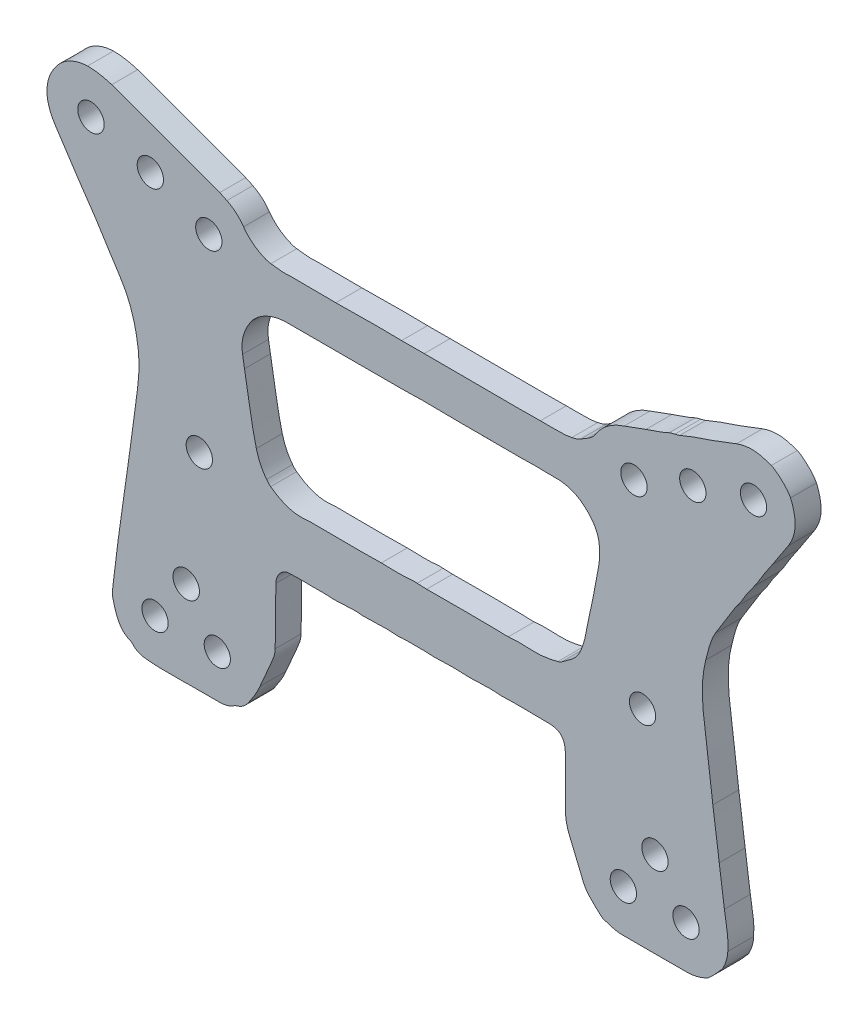
SolidWorks part; units mm, degrees
ref_plane "Front Plane" through (0, 0, 0) normal (0, 0, 1) x (1, 0, 0)
ref_plane "Top Plane" through (0, 0, 0) normal (0, 1, 0) x (1, 0, 0)
ref_plane "Right Plane" through (0, 0, 0) normal (1, 0, 0) x (0, 0, -1)
sketch "Model" plane through (0, 0, 0) normal (0, 0, 1) x (1, 0, 0)
  line L0 (97.8366, 172.2315) -> (110.3202, 167.6614)
  line L1 (138.5537, 158.5268) -> (149.5237, 158.5046)
  line L2 (118.384, 158.5261) -> (142.6959, 158.5291)
  circle A0 centre (95.4309, 167.7888) radius 1.5304
  circle A1 centre (102.2995, 165.6819) radius 1.5241
  circle A2 centre (109.0626, 162.8443) radius 1.5213
  circle A3 centre (158.2387, 162.8424) radius 1.5235
  circle A4 centre (165.0434, 165.6588) radius 1.5236
  circle A5 centre (172.0646, 167.7518) radius 1.5232
  circle A6 centre (159.2267, 140.4078) radius 1.5181
  circle A7 centre (107.9617, 140.4627) radius 1.5202
  circle A8 centre (102.8428, 121.5314) radius 1.5152
  circle A9 centre (110.0426, 121.522) radius 1.515
  circle A10 centre (106.448, 126.5199) radius 1.531
  circle A11 centre (160.6629, 126.5138) radius 1.5206
  circle A12 centre (157.0119, 121.5008) radius 1.522
  circle A13 centre (164.2554, 121.513) radius 1.5157
  spline S0 degree 2 poles (95.0441, 172.7052) (96.4811, 172.6765) (97.8366, 172.2315) knots 0 0 0 1 1 1
  spline S1 degree 2 poles (110.3202, 167.6614) (112.1413, 166.9415) (113.1909, 165.4568) knots 0 0 0 1 1 1
  spline S85 degree 3 poles (103.4626, 116.5865) (104.4481, 116.5653) (105.4344, 116.5808) (106.4204, 116.5808) knots 115 115 115 115 116 116 116 116
  spline S86 degree 3 poles (101.611, 116.719) (102.2249, 116.6461) (102.8445, 116.5998) (103.4626, 116.5865) knots 114 114 114 114 115 115 115 115
  spline S87 degree 3 poles (100.2756, 117.3777) (100.6348, 116.9744) (101.0987, 116.7799) (101.611, 116.719) knots 113 113 113 113 114 114 114 114
  spline S88 degree 3 poles (99.8652, 117.6628) (100.0163, 117.5998) (100.1675, 117.4992) (100.2756, 117.3777) knots 112 112 112 112 113 113 113 113
  spline S89 degree 3 poles (98.4441, 119.2638) (98.7327, 118.5809) (99.1304, 117.9689) (99.8652, 117.6628) knots 111 111 111 111 112 112 112 112
  spline S90 degree 3 poles (97.9974, 120.7159) (98.1355, 120.2283) (98.2479, 119.7279) (98.4441, 119.2638) knots 110 110 110 110 111 111 111 111
  spline S91 degree 3 poles (98.5644, 126.9173) (98.3475, 125.2708) (98.1634, 123.62) (97.9521, 121.9727) (97.8976, 121.5475) (97.8803, 121.1292) (97.9974, 120.7159) knots 108 108 108 108 109 109 109 110 110 110 110
  spline S92 degree 3 poles (99.279, 132.023) (99.0385, 130.3214) (98.7888, 128.621) (98.5644, 126.9173) knots 107 107 107 107 108 108 108 108
  spline S93 degree 3 poles (99.71, 135.0345) (99.5692, 134.0303) (99.421, 133.0271) (99.279, 132.023) knots 106 106 106 106 107 107 107 107
  spline S94 degree 3 poles (100.9053, 147.204) (101.0652, 145.9154) (100.9832, 144.613) (100.8239, 143.3237) (100.6236, 141.7024) (100.3996, 140.0841) (100.1819, 138.4651) (100.0282, 137.3211) (99.8702, 136.1776) (99.71, 135.0345) knots 103 103 103 103 104 104 104 105 105 105 106 106 106 106
  spline S95 degree 3 poles (98.7922, 153.4778) (100.0504, 151.5722) (100.6288, 149.4314) (100.9053, 147.204) knots 102 102 102 102 103 103 103 103
  spline S96 degree 3 poles (97.5576, 155.3954) (97.9657, 154.7539) (98.3733, 154.1122) (98.7922, 153.4778) knots 101 101 101 101 102 102 102 102
  spline S97 degree 3 poles (96.0248, 157.8234) (96.0565, 157.7768) (96.0853, 157.7282) (96.1154, 157.6806) (96.5959, 156.9187) (97.0742, 156.1554) (97.5576, 155.3954) knots 99 99 99 99 100 100 100 101 101 101 101
  spline S98 degree 3 poles (93.84, 161.0383) (94.5617, 159.9622) (95.2962, 158.8948) (96.0248, 157.8234) knots 98 98 98 98 99 99 99 99
  spline S99 degree 3 poles (91.5674, 164.5) (91.7649, 164.192) (91.9685, 163.8879) (92.1693, 163.5819) (92.7257, 162.7337) (93.275, 161.8807) (93.84, 161.0383) knots 96 96 96 96 97 97 97 98 98 98 98
  spline S100 degree 3 poles (90.9869, 165.4325) (91.1606, 165.111) (91.3697, 164.8083) (91.5674, 164.5) knots 95 95 95 95 96 96 96 96
  spline S101 degree 3 poles (95.0441, 172.7052) (93.229, 172.6106) (91.841, 171.7447) (90.9786, 170.2059) (90.114, 168.663) (90.1293, 167.02) (90.9869, 165.4325) knots 93 93 93 93 94 94 94 95 95 95 95
  spline S102 degree 3 poles (96.0103, 172.4602) (95.6857, 172.5087) (95.4054, 172.7241) (95.0441, 172.7052) knots 92 92 92 92 93 93 93 93 construction
  spline S103 degree 3 poles (96.927, 172.4812) (96.6208, 172.4791) (96.3079, 172.4157) (96.0103, 172.4602) knots 91 91 91 91 92 92 92 92 construction
  spline S104 degree 3 poles (98.9897, 171.7424) (98.3769, 171.9508) (97.7507, 172.1161) (97.1662, 172.4023) (97.091, 172.4392) (97.0067, 172.4818) (96.927, 172.4812) knots 89 89 89 89 90 90 90 91 91 91 91
  spline S105 degree 3 poles (101.6624, 170.6911) (100.773, 171.0459) (99.8951, 171.4344) (98.9897, 171.7424) knots 88 88 88 88 89 89 89 89
  spline S106 degree 3 poles (101.8161, 170.6222) (101.7627, 170.6298) (101.7147, 170.6702) (101.6624, 170.6911) knots 87 87 87 87 88 88 88 88
  spline S107 degree 3 poles (104.6139, 169.6781) (103.6743, 169.9742) (102.8069, 170.4816) (101.8161, 170.6222) knots 86 86 86 86 87 87 87 87
  spline S108 degree 3 poles (107.4638, 168.6149) (106.5143, 168.9714) (105.5796, 169.3738) (104.6139, 169.6781) knots 85 85 85 85 86 86 86 86
  spline S109 degree 3 poles (108.3376, 168.305) (108.0458, 168.4068) (107.7531, 168.5063) (107.4638, 168.6149) knots 84 84 84 84 85 85 85 85
  spline S110 degree 3 poles (109.5336, 167.8891) (109.1368, 168.033) (108.7361, 168.1659) (108.3376, 168.305) knots 83 83 83 83 84 84 84 84
  spline S111 degree 3 poles (110.3202, 167.5828) (110.0506, 167.6588) (109.7981, 167.7932) (109.5336, 167.8891) knots 82 82 82 82 83 83 83 83
  spline S112 degree 3 poles (113.0796, 165.6093) (112.3882, 166.5926) (111.4799, 167.2557) (110.3202, 167.5828) knots 81 81 81 81 82 82 82 82
  spline S113 degree 3 poles (116.2355, 163.4985) (116.0147, 163.5296) (115.7899, 163.5808) (115.5847, 163.6657) (114.5736, 164.084) (113.7131, 164.7082) (113.0796, 165.6093) knots 79 79 79 79 80 80 80 81 81 81 81
  spline S114 degree 3 poles (123.7475, 163.3393) (122.1428, 163.3359) (120.5381, 163.3604) (118.9334, 163.3717) (118.7643, 163.3729) (118.5941, 163.3786) (118.426, 163.3642) (117.6889, 163.3012) (116.9615, 163.3966) (116.2355, 163.4985) knots 76 76 76 76 77 77 77 78 78 78 79 79 79 79
  spline S115 degree 3 poles (131.3554, 163.3539) (130.4536, 163.3588) (129.5517, 163.3926) (128.65, 163.3884) (127.0158, 163.3809) (125.3817, 163.3426) (123.7475, 163.3393) knots 74 74 74 74 75 75 75 76 76 76 76
  spline S116 degree 3 poles (133.9742, 163.362) (133.1013, 163.3641) (132.2283, 163.3491) (131.3554, 163.3539) knots 73 73 73 73 74 74 74 74
  spline S117 degree 3 poles (147.4146, 163.3507) (145.5577, 163.2892) (143.6967, 163.3532) (141.8374, 163.3579) (141.0485, 163.3599) (140.2594, 163.34) (139.4704, 163.3415) (137.6383, 163.3449) (135.8063, 163.3577) (133.9742, 163.362) knots 70 70 70 70 71 71 71 72 72 72 73 73 73 73
  spline S118 degree 3 poles (151.0431, 163.4841) (149.8395, 163.2374) (148.6229, 163.3906) (147.4146, 163.3507) knots 69 69 69 69 70 70 70 70
  spline S119 degree 3 poles (152.0682, 163.85) (151.7528, 163.6502) (151.4083, 163.5589) (151.0431, 163.4841) knots 68 68 68 68 69 69 69 69
  spline S120 degree 3 poles (152.8653, 164.3297) (152.5965, 164.1751) (152.3301, 164.016) (152.0682, 163.85) knots 67 67 67 67 68 68 68 68
  spline S121 degree 3 poles (153.8953, 165.3107) (153.6303, 164.8973) (153.2891, 164.5735) (152.8653, 164.3297) knots 66 66 66 66 67 67 67 67
  spline S122 degree 3 poles (157.0904, 167.6614) (155.7611, 167.2261) (154.6586, 166.5011) (153.8953, 165.3107) knots 65 65 65 65 66 66 66 66
  spline S123 degree 3 poles (159.6279, 168.594) (158.7861, 168.2724) (157.9463, 167.9416) (157.0904, 167.6614) knots 64 64 64 64 65 65 65 65
  spline S124 degree 3 poles (162.3171, 169.5994) (161.4534, 169.1745) (160.5217, 168.9354) (159.6279, 168.594) knots 63 63 63 63 64 64 64 64
  spline S125 degree 3 poles (162.9657, 169.7875) (162.7485, 169.727) (162.516, 169.6972) (162.3171, 169.5994) knots 62 62 62 62 63 63 63 63
  spline S126 degree 3 poles (163.5345, 169.9491) (163.3555, 169.871) (163.1557, 169.8406) (162.9657, 169.7875) knots 61 61 61 61 62 62 62 62
  spline S127 degree 3 poles (170.0977, 172.3863) (169.1745, 172.049) (168.2721, 171.6518) (167.3408, 171.3399) (166.0587, 170.9106) (164.7751, 170.4909) (163.5345, 169.9491) knots 59 59 59 59 60 60 60 61 61 61 61
  spline S128 degree 3 poles (174.1315, 172.2315) (173.8233, 172.364) (173.4887, 172.4355) (173.1653, 172.5323) (172.1259, 172.8434) (171.1013, 172.7529) (170.0977, 172.3863) knots 57 57 57 57 58 58 58 59 59 59 59
  spline S129 degree 3 poles (176.3428, 170.088) (176.0534, 170.7614) (174.8057, 171.9416) (174.1315, 172.2315) knots 56 56 56 56 57 57 57 57
  spline S130 degree 3 poles (176.0878, 165.1701) (177.1359, 166.7607) (177.062, 168.4146) (176.3428, 170.088) knots 55 55 55 55 56 56 56 56
  spline S131 degree 3 poles (174.2803, 162.413) (174.9051, 163.3166) (175.4831, 164.2524) (176.0878, 165.1701) knots 54 54 54 54 55 55 55 55
  spline S132 degree 3 poles (172.2116, 159.2264) (172.315, 159.3598) (172.4182, 159.4961) (172.5007, 159.6428) (173.04, 160.601) (173.6553, 161.509) (174.2803, 162.413) knots 52 52 52 52 53 53 53 54 54 54 54
  spline S133 degree 3 poles (169.9768, 155.9499) (170.2168, 156.3303) (170.5443, 156.6596) (170.7558, 157.0531) (171.1719, 157.827) (171.6763, 158.5353) (172.2116, 159.2264) knots 50 50 50 50 51 51 51 52 52 52 52
  spline S134 degree 3 poles (167.6641, 152.2135) (168.4105, 153.4736) (169.1952, 154.7112) (169.9768, 155.9499) knots 49 49 49 49 50 50 50 50
  spline S135 degree 3 poles (166.5414, 148.9484) (166.829, 150.0678) (167.0683, 151.2077) (167.6641, 152.2135) knots 48 48 48 48 49 49 49 49
  spline S136 degree 3 poles (167.3622, 134.8553) (167.039, 137.3418) (166.7576, 139.8341) (166.4095, 142.317) (166.098, 144.5395) (165.9756, 146.7465) (166.5414, 148.9484) knots 46 46 46 46 47 47 47 48 48 48 48
  spline S137 degree 3 poles (168.1024, 129.4132) (167.8552, 131.2272) (167.5982, 133.0399) (167.3622, 134.8553) knots 45 45 45 45 46 46 46 46
  spline S138 degree 3 poles (168.6967, 125.0588) (168.4941, 126.5096) (168.3003, 127.9617) (168.1024, 129.4132) knots 44 44 44 44 45 45 45 45
  spline S139 degree 3 poles (169.0903, 121.0302) (169.1374, 121.7928) (169.093, 122.551) (168.9711, 123.3052) (168.8766, 123.8893) (168.7785, 124.4729) (168.6967, 125.0588) knots 42 42 42 42 43 43 43 44 44 44 44
  spline S140 degree 3 poles (168.5403, 119.0942) (168.865, 119.699) (169.0481, 120.3456) (169.0903, 121.0302) knots 41 41 41 41 42 42 42 42
  spline S141 degree 3 poles (166.6884, 117.1694) (167.0172, 117.3268) (168.3638, 118.7654) (168.5403, 119.0942) knots 40 40 40 40 41 41 41 41
  spline S142 degree 3 poles (164.4163, 116.5922) (165.2222, 116.5939) (165.9724, 116.8265) (166.6884, 117.1694) knots 39 39 39 39 40 40 40 40
  spline S143 degree 3 poles (160.2751, 116.5835) (161.6555, 116.584) (163.0359, 116.5894) (164.4163, 116.5922) knots 38 38 38 38 39 39 39 39
  spline S144 degree 3 poles (156.9781, 116.5886) (158.077, 116.5974) (159.1761, 116.5832) (160.2751, 116.5835) knots 37 37 37 37 38 38 38 38
  spline S145 degree 3 poles (154.8394, 117.0365) (155.5312, 116.7896) (156.2297, 116.5826) (156.9781, 116.5886) knots 36 36 36 36 37 37 37 37
  spline S146 degree 3 poles (154.4647, 117.2278) (154.5635, 117.1356) (154.7078, 117.0835) (154.8394, 117.0365) knots 35 35 35 35 36 36 36 36
  spline S147 degree 3 poles (150.8219, 123.3676) (151.3424, 122.1813) (151.8534, 120.9894) (152.3183, 119.7805) (152.7443, 118.6728) (153.6466, 117.9908) (154.4647, 117.2278) knots 33 33 33 33 34 34 34 35 35 35 35
  spline S148 degree 3 poles (150.3007, 131.3201) (150.3065, 129.573) (150.3247, 127.8255) (150.2967, 126.0789) (150.2814, 125.13) (150.4405, 124.2371) (150.8219, 123.3676) knots 31 31 31 31 32 32 32 33 33 33 33
  spline S149 degree 3 poles (150.2382, 132.1611) (150.2907, 131.8866) (150.2998, 131.6008) (150.3007, 131.3201) knots 30 30 30 30 31 31 31 31
  spline S150 degree 3 poles (148.8195, 133.5056) (149.6269, 133.3925) (150.0835, 132.97) (150.2382, 132.1611) knots 29 29 29 29 30 30 30 30
  spline S151 degree 3 poles (148.3977, 133.5344) (148.5383, 133.5356) (148.6802, 133.5251) (148.8195, 133.5056) knots 28 28 28 28 29 29 29 29
  spline S152 degree 3 poles (143.0806, 133.5385) (144.853, 133.632) (146.6253, 133.519) (148.3977, 133.5344) knots 27 27 27 27 28 28 28 28
  spline S153 degree 3 poles (142.9116, 133.5344) (142.9669, 133.5275) (143.0243, 133.5355) (143.0806, 133.5385) knots 26 26 26 26 27 27 27 27
  spline S154 degree 3 poles (140.216, 133.5696) (141.1149, 133.5884) (142.0142, 133.6459) (142.9116, 133.5344) knots 25 25 25 25 26 26 26 26
  spline S155 degree 3 poles (138.7829, 133.554) (139.2551, 133.5055) (139.7379, 133.5596) (140.216, 133.5696) knots 24 24 24 24 25 25 25 25
  spline S156 degree 3 poles (136.4213, 133.5814) (137.2082, 133.5757) (137.994, 133.635) (138.7829, 133.554) knots 23 23 23 23 24 24 24 24
  spline S157 degree 3 poles (134.7325, 133.5555) (135.2906, 133.5081) (135.8582, 133.5854) (136.4213, 133.5814) knots 22 22 22 22 23 23 23 23
  spline S158 degree 3 poles (131.4408, 133.5777) (131.6658, 133.5885) (131.8917, 133.6089) (132.116, 133.5983) (132.9875, 133.5572) (133.8592, 133.6297) (134.7325, 133.5555) knots 20 20 20 20 21 21 21 22 22 22 22
  spline S159 degree 3 poles (124.8834, 133.5663) (125.5278, 133.6167) (126.1648, 133.655) (126.8054, 133.5397) (126.9409, 133.5154) (127.0863, 133.5478) (127.2272, 133.5509) (127.5644, 133.5582) (127.9016, 133.5629) (128.2388, 133.5701) (129.1096, 133.5888) (129.9801, 133.655) (130.8508, 133.5448) (131.0429, 133.5205) (131.2437, 133.5683) (131.4408, 133.5777) knots 15 15 15 15 16 16 16 17 17 17 18 18 18 19 19 19 20 20 20 20
  spline S160 degree 3 poles (117.6073, 133.2911) (117.7791, 133.4179) (118.0084, 133.5206) (118.2175, 133.533) (118.8635, 133.5715) (119.5142, 133.5959) (120.1597, 133.5614) (121.0877, 133.5117) (122.0128, 133.6351) (122.9438, 133.5406) (123.5834, 133.4757) (124.2393, 133.5159) (124.8834, 133.5663) knots 11 11 11 11 12 12 12 13 13 13 14 14 14 15 15 15 15
  spline S161 degree 3 poles (116.8176, 131.7675) (116.8395, 132.3921) (117.102, 132.918) (117.6073, 133.2911) knots 10 10 10 10 11 11 11 11
  spline S162 degree 3 poles (116.7397, 125.1741) (116.7777, 126.5824) (116.7685, 127.9919) (116.7809, 129.4008) (116.7879, 130.1898) (116.7898, 130.9792) (116.8176, 131.7675) knots 8 8 8 8 9 9 9 10 10 10 10
  spline S163 degree 3 poles (114.9841, 120.5383) (115.4617, 121.7116) (116.0072, 122.8572) (116.4887, 124.0291) (116.6354, 124.3863) (116.7293, 124.7892) (116.7397, 125.1741) knots 6 6 6 6 7 7 7 8 8 8 8
  spline S164 degree 3 poles (113.6809, 118.2724) (114.1733, 118.9917) (114.6509, 119.7196) (114.9841, 120.5383) knots 5 5 5 5 6 6 6 6
  spline S165 degree 3 poles (112.3684, 117.2543) (112.9363, 117.4275) (113.3597, 117.8031) (113.6809, 118.2724) knots 4 4 4 4 5 5 5 5
  spline S166 degree 3 poles (106.4205, 116.5984) (107.6601, 116.5984) (108.8998, 116.6054) (110.1394, 116.5956) (110.8025, 116.5904) (111.4279, 116.6881) (111.9806, 117.0902) (112.0913, 117.1707) (112.2343, 117.2135) (112.3684, 117.2543) knots 1 1 1 1 2 2 2 3 3 3 4 4 4 4
  spline S167 degree 3 poles (106.4204, 116.5808) (106.4204, 116.5867) (106.4205, 116.5926) (106.4205, 116.5984) knots 0 0 0 0 1 1 1 1
  spline S341 degree 3 poles (106.4205, 116.5984) (106.4205, 116.5926) (106.4204, 116.5867) (106.4204, 116.5808) knots 115 115 115 115 116 116 116 116
  spline S342 degree 3 poles (112.3684, 117.2543) (112.2343, 117.2135) (112.0913, 117.1707) (111.9806, 117.0902) (111.4279, 116.6881) (110.8025, 116.5904) (110.1394, 116.5956) (108.8998, 116.6054) (107.6601, 116.5984) (106.4205, 116.5984) knots 112 112 112 112 113 113 113 114 114 114 115 115 115 115
  spline S343 degree 3 poles (113.6809, 118.2724) (113.3597, 117.8031) (112.9363, 117.4275) (112.3684, 117.2543) knots 111 111 111 111 112 112 112 112
  spline S344 degree 3 poles (114.9841, 120.5383) (114.6509, 119.7196) (114.1733, 118.9917) (113.6809, 118.2724) knots 110 110 110 110 111 111 111 111
  spline S345 degree 3 poles (116.7397, 125.1741) (116.7293, 124.7892) (116.6354, 124.3863) (116.4887, 124.0291) (116.0072, 122.8572) (115.4617, 121.7116) (114.9841, 120.5383) knots 108 108 108 108 109 109 109 110 110 110 110
  spline S346 degree 3 poles (116.8176, 131.7675) (116.7898, 130.9792) (116.7879, 130.1898) (116.7809, 129.4008) (116.7685, 127.9919) (116.7777, 126.5824) (116.7397, 125.1741) knots 106 106 106 106 107 107 107 108 108 108 108
  spline S347 degree 3 poles (117.6073, 133.2911) (117.102, 132.918) (116.8395, 132.3921) (116.8176, 131.7675) knots 105 105 105 105 106 106 106 106
  spline S348 degree 3 poles (124.8834, 133.5663) (124.2393, 133.5159) (123.5834, 133.4757) (122.9438, 133.5406) (122.0128, 133.6351) (121.0877, 133.5117) (120.1597, 133.5614) (119.5142, 133.5959) (118.8635, 133.5715) (118.2175, 133.533) (118.0084, 133.5206) (117.7791, 133.4179) (117.6073, 133.2911) knots 101 101 101 101 102 102 102 103 103 103 104 104 104 105 105 105 105
  spline S349 degree 3 poles (131.4408, 133.5777) (131.2437, 133.5683) (131.0429, 133.5205) (130.8508, 133.5448) (129.9801, 133.655) (129.1096, 133.5888) (128.2388, 133.5701) (127.9016, 133.5629) (127.5644, 133.5582) (127.2272, 133.5509) (127.0863, 133.5478) (126.9409, 133.5154) (126.8054, 133.5397) (126.1648, 133.655) (125.5278, 133.6167) (124.8834, 133.5663) knots 96 96 96 96 97 97 97 98 98 98 99 99 99 100 100 100 101 101 101 101
  spline S350 degree 3 poles (134.7325, 133.5555) (133.8592, 133.6297) (132.9875, 133.5572) (132.116, 133.5983) (131.8917, 133.6089) (131.6658, 133.5885) (131.4408, 133.5777) knots 94 94 94 94 95 95 95 96 96 96 96
  spline S351 degree 3 poles (136.4213, 133.5814) (135.8582, 133.5854) (135.2906, 133.5081) (134.7325, 133.5555) knots 93 93 93 93 94 94 94 94
  spline S352 degree 3 poles (138.7829, 133.554) (137.994, 133.635) (137.2082, 133.5757) (136.4213, 133.5814) knots 92 92 92 92 93 93 93 93
  spline S353 degree 3 poles (140.216, 133.5696) (139.7379, 133.5596) (139.2551, 133.5055) (138.7829, 133.554) knots 91 91 91 91 92 92 92 92
  spline S354 degree 3 poles (142.9116, 133.5344) (142.0142, 133.6459) (141.1149, 133.5884) (140.216, 133.5696) knots 90 90 90 90 91 91 91 91
  spline S355 degree 3 poles (143.0806, 133.5385) (143.0243, 133.5355) (142.9669, 133.5275) (142.9116, 133.5344) knots 89 89 89 89 90 90 90 90
  spline S356 degree 3 poles (148.3977, 133.5344) (146.6253, 133.519) (144.853, 133.632) (143.0806, 133.5385) knots 88 88 88 88 89 89 89 89
  spline S357 degree 3 poles (148.8195, 133.5056) (148.6802, 133.5251) (148.5383, 133.5356) (148.3977, 133.5344) knots 87 87 87 87 88 88 88 88
  spline S358 degree 3 poles (150.2382, 132.1611) (150.0835, 132.97) (149.6269, 133.3925) (148.8195, 133.5056) knots 86 86 86 86 87 87 87 87
  spline S359 degree 3 poles (150.3007, 131.3201) (150.2998, 131.6008) (150.2907, 131.8866) (150.2382, 132.1611) knots 85 85 85 85 86 86 86 86
  spline S360 degree 3 poles (150.8219, 123.3676) (150.4405, 124.2371) (150.2814, 125.13) (150.2967, 126.0789) (150.3247, 127.8255) (150.3065, 129.573) (150.3007, 131.3201) knots 83 83 83 83 84 84 84 85 85 85 85
  spline S361 degree 3 poles (154.4647, 117.2278) (153.6466, 117.9908) (152.7443, 118.6728) (152.3183, 119.7805) (151.8534, 120.9894) (151.3424, 122.1813) (150.8219, 123.3676) knots 81 81 81 81 82 82 82 83 83 83 83
  spline S362 degree 3 poles (154.8394, 117.0365) (154.7078, 117.0835) (154.5635, 117.1356) (154.4647, 117.2278) knots 80 80 80 80 81 81 81 81
  spline S363 degree 3 poles (156.9781, 116.5886) (156.2297, 116.5826) (155.5312, 116.7896) (154.8394, 117.0365) knots 79 79 79 79 80 80 80 80
  spline S364 degree 3 poles (160.2751, 116.5835) (159.1761, 116.5832) (158.077, 116.5974) (156.9781, 116.5886) knots 78 78 78 78 79 79 79 79
  spline S365 degree 3 poles (164.4163, 116.5922) (163.0359, 116.5894) (161.6555, 116.584) (160.2751, 116.5835) knots 77 77 77 77 78 78 78 78
  spline S366 degree 3 poles (166.6884, 117.1694) (165.9724, 116.8265) (165.2222, 116.5939) (164.4163, 116.5922) knots 76 76 76 76 77 77 77 77
  spline S367 degree 3 poles (168.5403, 119.0942) (168.3638, 118.7654) (167.0172, 117.3268) (166.6884, 117.1694) knots 75 75 75 75 76 76 76 76
  spline S368 degree 3 poles (169.0903, 121.0302) (169.0481, 120.3456) (168.865, 119.699) (168.5403, 119.0942) knots 74 74 74 74 75 75 75 75
  spline S369 degree 3 poles (168.6967, 125.0588) (168.7785, 124.4729) (168.8766, 123.8893) (168.9711, 123.3052) (169.093, 122.551) (169.1374, 121.7928) (169.0903, 121.0302) knots 72 72 72 72 73 73 73 74 74 74 74
  spline S370 degree 3 poles (168.1024, 129.4132) (168.3003, 127.9617) (168.4941, 126.5096) (168.6967, 125.0588) knots 71 71 71 71 72 72 72 72
  spline S371 degree 3 poles (167.3622, 134.8553) (167.5982, 133.0399) (167.8552, 131.2272) (168.1024, 129.4132) knots 70 70 70 70 71 71 71 71
  spline S372 degree 3 poles (166.5414, 148.9484) (165.9756, 146.7465) (166.098, 144.5395) (166.4095, 142.317) (166.7576, 139.8341) (167.039, 137.3418) (167.3622, 134.8553) knots 68 68 68 68 69 69 69 70 70 70 70
  spline S373 degree 3 poles (167.6641, 152.2135) (167.0683, 151.2077) (166.829, 150.0678) (166.5414, 148.9484) knots 67 67 67 67 68 68 68 68
  spline S374 degree 3 poles (169.9768, 155.9499) (169.1952, 154.7112) (168.4105, 153.4736) (167.6641, 152.2135) knots 66 66 66 66 67 67 67 67
  spline S375 degree 3 poles (172.2116, 159.2264) (171.6763, 158.5353) (171.1719, 157.827) (170.7558, 157.0531) (170.5443, 156.6596) (170.2168, 156.3303) (169.9768, 155.9499) knots 64 64 64 64 65 65 65 66 66 66 66
  spline S376 degree 3 poles (174.2803, 162.413) (173.6553, 161.509) (173.04, 160.601) (172.5007, 159.6428) (172.4182, 159.4961) (172.315, 159.3598) (172.2116, 159.2264) knots 62 62 62 62 63 63 63 64 64 64 64
  spline S377 degree 3 poles (176.0878, 165.1701) (175.4831, 164.2524) (174.9051, 163.3166) (174.2803, 162.413) knots 61 61 61 61 62 62 62 62
  spline S378 degree 3 poles (176.3428, 170.088) (177.062, 168.4146) (177.1359, 166.7607) (176.0878, 165.1701) knots 60 60 60 60 61 61 61 61
  spline S379 degree 3 poles (174.1315, 172.2315) (174.8057, 171.9416) (176.0534, 170.7614) (176.3428, 170.088) knots 59 59 59 59 60 60 60 60
  spline S380 degree 3 poles (170.0977, 172.3863) (171.1013, 172.7529) (172.1259, 172.8434) (173.1653, 172.5323) (173.4887, 172.4355) (173.8233, 172.364) (174.1315, 172.2315) knots 57 57 57 57 58 58 58 59 59 59 59
  spline S381 degree 3 poles (163.5345, 169.9491) (164.7751, 170.4909) (166.0587, 170.9106) (167.3408, 171.3399) (168.2721, 171.6518) (169.1745, 172.049) (170.0977, 172.3863) knots 55 55 55 55 56 56 56 57 57 57 57
  spline S382 degree 3 poles (162.9657, 169.7875) (163.1557, 169.8406) (163.3555, 169.871) (163.5345, 169.9491) knots 54 54 54 54 55 55 55 55
  spline S383 degree 3 poles (162.3171, 169.5994) (162.516, 169.6972) (162.7485, 169.727) (162.9657, 169.7875) knots 53 53 53 53 54 54 54 54
  spline S384 degree 3 poles (159.6279, 168.594) (160.5217, 168.9354) (161.4534, 169.1745) (162.3171, 169.5994) knots 52 52 52 52 53 53 53 53
  spline S385 degree 3 poles (157.0904, 167.6614) (157.9463, 167.9416) (158.7861, 168.2724) (159.6279, 168.594) knots 51 51 51 51 52 52 52 52
  spline S386 degree 3 poles (153.8953, 165.3107) (154.6586, 166.5011) (155.7611, 167.2261) (157.0904, 167.6614) knots 50 50 50 50 51 51 51 51
  spline S387 degree 3 poles (152.8653, 164.3297) (153.2891, 164.5735) (153.6303, 164.8973) (153.8953, 165.3107) knots 49 49 49 49 50 50 50 50
  spline S388 degree 3 poles (152.0682, 163.85) (152.3301, 164.016) (152.5965, 164.1751) (152.8653, 164.3297) knots 48 48 48 48 49 49 49 49
  spline S389 degree 3 poles (151.0431, 163.4841) (151.4083, 163.5589) (151.7528, 163.6502) (152.0682, 163.85) knots 47 47 47 47 48 48 48 48
  spline S390 degree 3 poles (147.4146, 163.3507) (148.6229, 163.3906) (149.8395, 163.2374) (151.0431, 163.4841) knots 46 46 46 46 47 47 47 47
  spline S391 degree 3 poles (133.9742, 163.362) (135.8063, 163.3577) (137.6383, 163.3449) (139.4704, 163.3415) (140.2594, 163.34) (141.0485, 163.3599) (141.8374, 163.3579) (143.6967, 163.3532) (145.5577, 163.2892) (147.4146, 163.3507) knots 43 43 43 43 44 44 44 45 45 45 46 46 46 46
  spline S392 degree 3 poles (131.3554, 163.3539) (132.2283, 163.3491) (133.1013, 163.3641) (133.9742, 163.362) knots 42 42 42 42 43 43 43 43
  spline S393 degree 3 poles (123.7475, 163.3393) (125.3817, 163.3426) (127.0158, 163.3809) (128.65, 163.3884) (129.5517, 163.3926) (130.4536, 163.3588) (131.3554, 163.3539) knots 40 40 40 40 41 41 41 42 42 42 42
  spline S394 degree 3 poles (116.2355, 163.4985) (116.9615, 163.3966) (117.6889, 163.3012) (118.426, 163.3642) (118.5941, 163.3786) (118.7643, 163.3729) (118.9334, 163.3717) (120.5381, 163.3604) (122.1428, 163.3359) (123.7475, 163.3393) knots 37 37 37 37 38 38 38 39 39 39 40 40 40 40
  spline S395 degree 3 poles (113.0796, 165.6093) (113.7131, 164.7082) (114.5736, 164.084) (115.5847, 163.6657) (115.7899, 163.5808) (116.0147, 163.5296) (116.2355, 163.4985) knots 35 35 35 35 36 36 36 37 37 37 37
  spline S396 degree 3 poles (110.3202, 167.5828) (111.4799, 167.2557) (112.3882, 166.5926) (113.0796, 165.6093) knots 34 34 34 34 35 35 35 35
  spline S397 degree 3 poles (109.5336, 167.8891) (109.7981, 167.7932) (110.0506, 167.6588) (110.3202, 167.5828) knots 33 33 33 33 34 34 34 34
  spline S398 degree 3 poles (108.3376, 168.305) (108.7361, 168.1659) (109.1368, 168.033) (109.5336, 167.8891) knots 32 32 32 32 33 33 33 33
  spline S399 degree 3 poles (107.4638, 168.6149) (107.7531, 168.5063) (108.0458, 168.4068) (108.3376, 168.305) knots 31 31 31 31 32 32 32 32
  spline S400 degree 3 poles (104.6139, 169.6781) (105.5796, 169.3738) (106.5143, 168.9714) (107.4638, 168.6149) knots 30 30 30 30 31 31 31 31
  spline S401 degree 3 poles (101.8161, 170.6222) (102.8069, 170.4816) (103.6743, 169.9742) (104.6139, 169.6781) knots 29 29 29 29 30 30 30 30
  spline S402 degree 3 poles (101.6624, 170.6911) (101.7147, 170.6702) (101.7627, 170.6298) (101.8161, 170.6222) knots 28 28 28 28 29 29 29 29
  spline S403 degree 3 poles (98.9897, 171.7424) (99.8951, 171.4344) (100.773, 171.0459) (101.6624, 170.6911) knots 27 27 27 27 28 28 28 28
  spline S404 degree 3 poles (96.927, 172.4812) (97.0067, 172.4818) (97.091, 172.4392) (97.1662, 172.4023) (97.7507, 172.1161) (98.3769, 171.9508) (98.9897, 171.7424) knots 25 25 25 25 26 26 26 27 27 27 27
  spline S405 degree 3 poles (96.0103, 172.4602) (96.3079, 172.4157) (96.6208, 172.4791) (96.927, 172.4812) knots 24 24 24 24 25 25 25 25 construction
  spline S406 degree 3 poles (95.0441, 172.7052) (95.4054, 172.7241) (95.6857, 172.5087) (96.0103, 172.4602) knots 23 23 23 23 24 24 24 24 construction
  spline S407 degree 3 poles (90.9869, 165.4325) (90.1293, 167.02) (90.114, 168.663) (90.9786, 170.2059) (91.841, 171.7447) (93.229, 172.6106) (95.0441, 172.7052) knots 21 21 21 21 22 22 22 23 23 23 23
  spline S408 degree 3 poles (91.5674, 164.5) (91.3697, 164.8083) (91.1606, 165.111) (90.9869, 165.4325) knots 20 20 20 20 21 21 21 21
  spline S409 degree 3 poles (93.84, 161.0383) (93.275, 161.8807) (92.7257, 162.7337) (92.1693, 163.5819) (91.9685, 163.8879) (91.7649, 164.192) (91.5674, 164.5) knots 18 18 18 18 19 19 19 20 20 20 20
  spline S410 degree 3 poles (96.0248, 157.8234) (95.2962, 158.8948) (94.5617, 159.9622) (93.84, 161.0383) knots 17 17 17 17 18 18 18 18
  spline S411 degree 3 poles (97.5576, 155.3954) (97.0742, 156.1554) (96.5959, 156.9187) (96.1154, 157.6806) (96.0853, 157.7282) (96.0565, 157.7768) (96.0248, 157.8234) knots 15 15 15 15 16 16 16 17 17 17 17
  spline S412 degree 3 poles (98.7922, 153.4778) (98.3733, 154.1122) (97.9657, 154.7539) (97.5576, 155.3954) knots 14 14 14 14 15 15 15 15
  spline S413 degree 3 poles (100.9053, 147.204) (100.6288, 149.4314) (100.0504, 151.5722) (98.7922, 153.4778) knots 13 13 13 13 14 14 14 14
  spline S414 degree 3 poles (99.71, 135.0345) (99.8702, 136.1776) (100.0282, 137.3211) (100.1819, 138.4651) (100.3996, 140.0841) (100.6236, 141.7024) (100.8239, 143.3237) (100.9832, 144.613) (101.0652, 145.9154) (100.9053, 147.204) knots 10 10 10 10 11 11 11 12 12 12 13 13 13 13
  spline S415 degree 3 poles (99.279, 132.023) (99.421, 133.0271) (99.5692, 134.0303) (99.71, 135.0345) knots 9 9 9 9 10 10 10 10
  spline S416 degree 3 poles (98.5644, 126.9173) (98.7888, 128.621) (99.0385, 130.3214) (99.279, 132.023) knots 8 8 8 8 9 9 9 9
  spline S417 degree 3 poles (97.9974, 120.7159) (97.8803, 121.1292) (97.8976, 121.5475) (97.9521, 121.9727) (98.1634, 123.62) (98.3475, 125.2708) (98.5644, 126.9173) knots 6 6 6 6 7 7 7 8 8 8 8
  spline S418 degree 3 poles (98.4441, 119.2638) (98.2479, 119.7279) (98.1355, 120.2283) (97.9974, 120.7159) knots 5 5 5 5 6 6 6 6
  spline S419 degree 3 poles (99.8652, 117.6628) (99.1304, 117.9689) (98.7327, 118.5809) (98.4441, 119.2638) knots 4 4 4 4 5 5 5 5
  spline S420 degree 3 poles (100.2756, 117.3777) (100.1675, 117.4992) (100.0163, 117.5998) (99.8652, 117.6628) knots 3 3 3 3 4 4 4 4
  spline S421 degree 3 poles (101.611, 116.719) (101.0987, 116.7799) (100.6348, 116.9744) (100.2756, 117.3777) knots 2 2 2 2 3 3 3 3
  spline S422 degree 3 poles (103.4626, 116.5865) (102.8445, 116.5998) (102.2249, 116.6461) (101.611, 116.719) knots 1 1 1 1 2 2 2 2
  spline S423 degree 3 poles (106.4204, 116.5808) (105.4344, 116.5808) (104.4481, 116.5653) (103.4626, 116.5865) knots 0 0 0 0 1 1 1 1
  spline S424 degree 3 poles (125.1436, 158.5521) (125.0112, 158.5163) (124.863, 158.5338) (124.7221, 158.5355) (123.7928, 158.5469) (122.8635, 158.561) (121.9341, 158.5733) (121.7654, 158.5755) (121.5966, 158.5736) (121.4279, 158.5736) knots 40 40 40 40 41 41 41 42 42 42 43 43 43 43
  spline S425 degree 3 poles (126.3915, 158.5317) (125.9758, 158.6497) (125.5644, 158.6658) (125.1436, 158.5521) knots 39 39 39 39 40 40 40 40
  spline S426 degree 3 poles (126.7278, 158.5055) (126.6156, 158.503) (126.4976, 158.5016) (126.3915, 158.5317) knots 38 38 38 38 39 39 39 39
  spline S427 degree 3 poles (129.431, 158.5718) (128.5299, 158.5484) (127.6289, 158.5253) (126.7278, 158.5055) knots 37 37 37 37 38 38 38 38
  spline S428 degree 3 poles (129.7681, 158.5901) (129.6574, 158.601) (129.5435, 158.5747) (129.431, 158.5718) knots 36 36 36 36 37 37 37 37
  spline S429 degree 3 poles (133.7374, 158.5745) (132.4141, 158.5662) (131.0911, 158.4596) (129.7681, 158.5901) knots 35 35 35 35 36 36 36 36
  spline S430 degree 3 poles (138.5537, 158.5268) (136.9482, 158.5372) (135.3427, 158.5846) (133.7374, 158.5745) knots 34 34 34 34 35 35 35 35
  spline S431 degree 3 poles (142.6959, 158.5291) (141.3152, 158.5237) (139.9344, 158.5179) (138.5537, 158.5268) knots 33 33 33 33 34 34 34 34
  spline S432 degree 3 poles (143.2836, 158.5843) (143.0876, 158.5662) (142.8919, 158.5299) (142.6959, 158.5291) knots 32 32 32 32 33 33 33 33
  spline S433 degree 3 poles (143.7828, 158.6205) (143.6247, 158.6513) (143.4503, 158.5998) (143.2836, 158.5843) knots 31 31 31 31 32 32 32 32
  spline S434 degree 3 poles (149.5237, 158.5046) (148.7086, 158.5472) (147.8891, 158.4999) (147.0733, 158.5346) (145.9771, 158.5811) (144.8757, 158.4077) (143.7828, 158.6205) knots 29 29 29 29 30 30 30 31 31 31 31
  spline S435 degree 3 poles (154.2394, 154.2012) (154.1778, 154.9436) (153.9411, 155.6529) (153.5047, 156.249) (152.5242, 157.5883) (151.2182, 158.4158) (149.5237, 158.5046) knots 27 27 27 27 28 28 28 29 29 29 29
  spline S436 degree 3 poles (154.1613, 152.1801) (154.2824, 152.8534) (154.2954, 153.5274) (154.2394, 154.2012) knots 26 26 26 26 27 27 27 27
  spline S437 degree 3 poles (152.9447, 146.0477) (153.413, 148.0795) (153.7923, 150.1285) (154.1613, 152.1801) knots 25 25 25 25 26 26 26 26
  spline S438 degree 3 poles (152.6966, 144.8043) (152.78, 145.2186) (152.8498, 145.636) (152.9447, 146.0477) knots 24 24 24 24 25 25 25 25
  spline S439 degree 3 poles (152.522, 143.9772) (152.598, 144.2479) (152.641, 144.528) (152.6966, 144.8043) knots 23 23 23 23 24 24 24 24
  spline S440 degree 3 poles (149.8835, 140.4396) (151.6168, 141.6204) (151.958, 141.9679) (152.522, 143.9772) knots 22 22 22 22 23 23 23 23
  spline S441 degree 3 poles (149.4228, 140.2334) (149.5842, 140.2682) (149.7461, 140.3461) (149.8835, 140.4396) knots 21 21 21 21 22 22 22 22
  spline S442 degree 3 poles (143.7148, 139.8592) (144.8145, 139.9743) (145.9128, 139.8782) (147.0095, 139.8661) (147.8455, 139.8569) (148.627, 140.0616) (149.4228, 140.2334) knots 19 19 19 19 20 20 20 21 21 21 21
  spline S443 degree 3 poles (134.2498, 139.8983) (135.1231, 139.8999) (135.9965, 139.9268) (136.8698, 139.9235) (138.7009, 139.9167) (140.5319, 139.8985) (142.3629, 139.8817) (142.8139, 139.8776) (143.2699, 139.8126) (143.7148, 139.8592) knots 16 16 16 16 17 17 17 18 18 18 19 19 19 19
  spline S444 degree 3 poles (133.1529, 139.9426) (133.5186, 139.9274) (133.8842, 139.8976) (134.2498, 139.8983) knots 15 15 15 15 16 16 16 16
  spline S445 degree 3 poles (129.0158, 139.9144) (130.2267, 139.9012) (131.4375, 139.8038) (132.6468, 139.9572) (132.8123, 139.9781) (132.9841, 139.9496) (133.1529, 139.9426) knots 13 13 13 13 14 14 14 15 15 15 15
  spline S446 degree 3 poles (116.2142, 141.1513) (117.4543, 140.2314) (118.8123, 139.6904) (120.3946, 139.8925) (120.6173, 139.921) (120.8451, 139.9156) (121.0705, 139.9144) (122.8456, 139.9051) (124.6207, 139.8873) (126.3959, 139.8841) (127.2692, 139.8825) (128.1427, 139.9238) (129.0158, 139.9144) knots 9 9 9 9 10 10 10 11 11 11 12 12 12 13 13 13 13
  spline S447 degree 3 poles (115.7516, 141.6405) (115.8898, 141.4642) (116.0365, 141.2831) (116.2142, 141.1513) knots 8 8 8 8 9 9 9 9
  spline S448 degree 3 poles (114.5587, 144.1377) (114.7918, 143.2202) (115.169, 142.3835) (115.7516, 141.6405) knots 7 7 7 7 8 8 8 8
  spline S449 degree 3 poles (113.1909, 151.4451) (113.6539, 149.0107) (113.9469, 146.5452) (114.5587, 144.1377) knots 6 6 6 6 7 7 7 7
  spline S450 degree 3 poles (112.9679, 152.7792) (113.0407, 152.3343) (113.1067, 151.8879) (113.1909, 151.4451) knots 5 5 5 5 6 6 6 6
  spline S451 degree 3 poles (113.8824, 156.4614) (113.1225, 155.3619) (112.7458, 154.137) (112.9679, 152.7792) knots 4 4 4 4 5 5 5 5
  spline S452 degree 3 poles (116.1461, 158.1703) (115.2323, 157.8253) (114.4381, 157.2655) (113.8824, 156.4614) knots 3 3 3 3 4 4 4 4
  spline S453 degree 3 poles (118.384, 158.5261) (117.6039, 158.5617) (116.8598, 158.4398) (116.1461, 158.1703) knots 2 2 2 2 3 3 3 3
  spline S454 degree 3 poles (121.4281, 158.5148) (120.4132, 158.5148) (119.3968, 158.4799) (118.384, 158.5261) knots 1 1 1 1 2 2 2 2
  spline S455 degree 3 poles (121.4279, 158.5736) (121.4279, 158.554) (121.428, 158.5344) (121.4281, 158.5148) knots 0 0 0 0 1 1 1 1
  spline S456 degree 3 poles (93.6822, 167.7807) (93.6855, 166.8559) (94.3794, 166.2527) (95.4333, 166.2584) knots 3 3 3 3 4 4 4 4 construction
  spline S457 degree 3 poles (95.4808, 169.4169) (94.4329, 169.3218) (93.679, 168.7016) (93.6822, 167.7807) knots 2 2 2 2 3 3 3 3 construction
  spline S458 degree 3 poles (96.96, 167.8519) (96.9685, 168.541) (96.1437, 169.4771) (95.4808, 169.4169) knots 1 1 1 1 2 2 2 2 construction
  spline S459 degree 3 poles (95.4333, 166.2584) (96.1471, 166.1793) (96.9491, 166.9679) (96.96, 167.8519) knots 0 0 0 0 1 1 1 1 construction
  spline S460 degree 3 poles (110.67, 162.7636) (110.7079, 163.673) (110.0467, 164.3462) (109.0968, 164.3652) knots 3 3 3 3 4 4 4 4 construction
  spline S461 degree 3 poles (107.4635, 162.8335) (107.4427, 161.9574) (108.1133, 161.2869) (108.9892, 161.2581) (109.9377, 161.227) (110.6318, 161.8487) (110.67, 162.7636) knots 1 1 1 1 2 2 2 3 3 3 3 construction
  spline S462 degree 3 poles (109.0968, 164.3652) (108.0469, 164.3699) (107.4852, 163.7437) (107.4635, 162.8335) knots 0 0 0 0 1 1 1 1 construction
  spline S463 degree 3 poles (165.6689, 164.2501) (166.2723, 164.5288) (166.607, 165.0405) (166.6238, 165.7041) knots 5 5 5 5 6 6 6 6 construction
  spline S464 degree 3 poles (164.0095, 164.5396) (164.4974, 164.1494) (165.0793, 163.9777) (165.6689, 164.2501) knots 4 4 4 4 5 5 5 5 construction
  spline S465 degree 3 poles (163.4757, 166.2098) (163.3149, 165.5542) (163.4755, 164.9667) (164.0095, 164.5396) knots 3 3 3 3 4 4 4 4 construction
  spline S466 degree 3 poles (165.8224, 167.0984) (165.1925, 167.3742) (164.2566, 167.2007) (163.7778, 166.7051) (163.6456, 166.5682) (163.5198, 166.3898) (163.4757, 166.2098) knots 1 1 1 1 2 2 2 3 3 3 3 construction
  spline S467 degree 3 poles (166.6238, 165.7041) (166.6076, 166.3324) (166.4188, 166.8373) (165.8224, 167.0984) knots 0 0 0 0 1 1 1 1 construction
  spline S468 degree 3 poles (102.3026, 167.3063) (101.451, 167.3298) (100.676, 166.5968) (100.6448, 165.7384) (100.6165, 164.9597) (101.3883, 164.1774) (102.2009, 164.161) knots 2 2 2 2 3 3 3 4 4 4 4 construction
  spline S469 degree 3 poles (102.2009, 164.161) (103.1002, 164.1429) (103.9183, 164.8663) (103.9097, 165.6719) (103.9004, 166.542) (103.1726, 167.2822) (102.3026, 167.3063) knots 0 0 0 0 1 1 1 2 2 2 2 construction
  spline S470 degree 3 poles (172.1629, 169.3289) (171.2039, 169.3653) (170.419, 168.6612) (170.4206, 167.7661) (170.422, 166.9504) (171.1039, 166.2528) (171.9166, 166.2358) knots 2 2 2 2 3 3 3 4 4 4 4 construction
  spline S471 degree 3 poles (173.6468, 167.8149) (173.6688, 168.6591) (173.0452, 169.2953) (172.1629, 169.3289) knots 1 1 1 1 2 2 2 2 construction
  spline S472 degree 3 poles (171.9166, 166.2358) (172.9032, 166.2152) (173.6222, 166.8714) (173.6468, 167.8149) knots 0 0 0 0 1 1 1 1 construction
  spline S473 degree 3 poles (157.6154, 140.5253) (157.5851, 139.6431) (158.2799, 138.918) (159.1821, 138.8903) knots 3 3 3 3 4 4 4 4 construction
  spline S474 degree 3 poles (159.3579, 142.0166) (158.4327, 142.0334) (157.644, 141.3584) (157.6154, 140.5253) knots 2 2 2 2 3 3 3 3 construction
  spline S475 degree 3 poles (160.7826, 140.404) (160.8144, 141.1982) (160.1033, 142.003) (159.3579, 142.0166) knots 1 1 1 1 2 2 2 2 construction
  spline S476 degree 3 poles (159.1821, 138.8903) (160.0334, 138.8643) (160.7482, 139.5402) (160.7826, 140.404) knots 0 0 0 0 1 1 1 1 construction
  spline S477 degree 3 poles (109.8683, 120.0171) (110.7532, 119.8387) (111.6684, 120.5917) (111.6738, 121.4729) knots 4 4 4 4 5 5 5 5 construction
  spline S478 degree 3 poles (109.096, 120.3391) (109.3287, 120.1911) (109.5993, 120.0713) (109.8683, 120.0171) knots 3 3 3 3 4 4 4 4 construction
  spline S479 degree 3 poles (111.6738, 121.4729) (111.678, 122.154) (111.1019, 122.8427) (110.3563, 123.0481) (109.7959, 123.2024) (108.9712, 122.8118) (108.6381, 122.2343) (108.2108, 121.4936) (108.3662, 120.8034) (109.096, 120.3391) knots 0 0 0 0 1 1 1 2 2 2 3 3 3 3 construction
  spline S480 degree 3 poles (108.0524, 138.8962) (108.8644, 138.9259) (109.5459, 139.6416) (109.5239, 140.4415) knots 3 3 3 3 4 4 4 4 construction
  spline S481 degree 3 poles (106.3539, 140.4013) (106.3703, 139.5385) (107.1329, 138.8626) (108.0524, 138.8962) knots 2 2 2 2 3 3 3 3 construction
  spline S482 degree 3 poles (109.5239, 140.4415) (109.4993, 141.3319) (108.7465, 142.0498) (107.8768, 142.0124) (107.0396, 141.9764) (106.3381, 141.2344) (106.3539, 140.4013) knots 0 0 0 0 1 1 1 2 2 2 2 construction
  spline S483 degree 3 poles (102.0444, 120.2436) (102.3122, 120.108) (102.6223, 120.0558) (102.7675, 120.0108) knots 4 4 4 4 5 5 5 5 construction
  spline S484 degree 3 poles (101.3139, 121.9403) (101.1037, 121.2735) (101.3863, 120.577) (102.0444, 120.2436) knots 3 3 3 3 4 4 4 4 construction
  spline S485 degree 3 poles (102.8934, 123.0457) (102.1371, 123.1082) (101.5537, 122.7007) (101.3139, 121.9403) knots 2 2 2 2 3 3 3 3 construction
  spline S486 degree 3 poles (102.7675, 120.0108) (103.6169, 120.0297) (104.0895, 120.3494) (104.3187, 120.9072) (104.6535, 121.7217) (104.2856, 122.9307) (102.8934, 123.0457) knots 0 0 0 0 1 1 1 2 2 2 2 construction
  spline S487 degree 3 poles (158.0821, 164.3579) (157.371, 164.3794) (156.6289, 163.4396) (156.6395, 162.8493) (156.6545, 162.0067) (157.3494, 161.2788) (158.1769, 161.2787) knots 2 2 2 2 3 3 3 4 4 4 4 construction
  spline S488 degree 3 poles (159.8171, 162.8134) (159.8183, 163.736) (159.1227, 164.3265) (158.0821, 164.3579) knots 1 1 1 1 2 2 2 2 construction
  spline S489 degree 3 poles (158.1769, 161.2787) (159.1405, 161.2785) (159.816, 161.9105) (159.8171, 162.8134) knots 0 0 0 0 1 1 1 1 construction
  spline S490 degree 3 poles (165.8048, 121.8296) (165.6271, 122.5774) (165.0439, 123.0062) (164.1768, 123.0267) knots 4 4 4 4 5 5 5 5 construction
  spline S491 degree 3 poles (164.6073, 120.0387) (165.5107, 120.1735) (166.0155, 120.9432) (165.8048, 121.8296) knots 3 3 3 3 4 4 4 4 construction
  spline S492 degree 3 poles (162.8366, 120.7833) (163.2709, 120.1889) (163.8746, 119.9294) (164.6073, 120.0387) knots 2 2 2 2 3 3 3 3 construction
  spline S493 degree 3 poles (162.6059, 121.4035) (162.6243, 121.1901) (162.7104, 120.9561) (162.8366, 120.7833) knots 1 1 1 1 2 2 2 2 construction
  spline S494 degree 3 poles (164.1768, 123.0267) (163.2292, 123.1201) (162.5456, 122.1007) (162.6059, 121.4035) knots 0 0 0 0 1 1 1 1 construction
  spline S495 degree 3 poles (158.4364, 122.2426) (158.1531, 122.7948) (157.6729, 123.0423) (156.8492, 123.014) knots 5 5 5 5 6 6 6 6 construction
  spline S496 degree 3 poles (158.1496, 120.3806) (158.19, 120.4192) (158.2291, 120.4604) (158.2628, 120.5049) (158.6749, 121.0485) (158.7475, 121.6364) (158.4364, 122.2426) knots 3 3 3 3 4 4 4 5 5 5 5 construction
  spline S497 degree 3 poles (155.9659, 120.3951) (156.5893, 119.893) (157.6326, 119.8857) (158.1496, 120.3806) knots 2 2 2 2 3 3 3 3 construction
  spline S498 degree 3 poles (155.6613, 122.3813) (155.2518, 121.7459) (155.3949, 120.855) (155.9659, 120.3951) knots 1 1 1 1 2 2 2 2 construction
  spline S499 degree 3 poles (156.8492, 123.014) (156.503, 122.9957) (155.9858, 122.8848) (155.6613, 122.3813) knots 0 0 0 0 1 1 1 1 construction
  spline S500 degree 3 poles (159.0467, 126.5472) (159.009, 125.696) (159.7582, 125.0055) (160.6901, 124.9934) knots 3 3 3 3 4 4 4 4 construction
  spline S501 degree 3 poles (160.6357, 128.0342) (159.56, 128.0199) (159.082, 127.3447) (159.0467, 126.5472) knots 2 2 2 2 3 3 3 3 construction
  spline S502 degree 3 poles (162.2154, 126.5271) (162.2251, 127.3649) (161.5152, 128.0459) (160.6357, 128.0342) knots 1 1 1 1 2 2 2 2 construction
  spline S503 degree 3 poles (160.6901, 124.9934) (161.5885, 124.9818) (162.2047, 125.6013) (162.2154, 126.5271) knots 0 0 0 0 1 1 1 1 construction
  spline S504 degree 3 poles (108.0334, 126.3932) (108.0689, 127.2934) (107.3819, 128.0287) (106.4851, 128.0505) knots 3 3 3 3 4 4 4 4 construction
  spline S505 degree 3 poles (106.5263, 124.9909) (107.3371, 124.9872) (108.0024, 125.6062) (108.0334, 126.3932) knots 2 2 2 2 3 3 3 3 construction
  spline S506 degree 3 poles (104.8438, 126.5392) (104.8138, 125.734) (105.6168, 124.9951) (106.5263, 124.9909) knots 1 1 1 1 2 2 2 2 construction
  spline S507 degree 3 poles (106.4851, 128.0505) (105.6797, 128.0701) (104.8731, 127.3273) (104.8438, 126.5392) knots 0 0 0 0 1 1 1 1 construction
  spline S600 degree 3 poles (121.4281, 158.5148) (121.428, 158.5344) (121.4279, 158.554) (121.4279, 158.5736) knots 42 42 42 42 43 43 43 43
  spline S601 degree 3 poles (118.384, 158.5261) (119.3968, 158.4799) (120.4132, 158.5148) (121.4281, 158.5148) knots 41 41 41 41 42 42 42 42
  spline S602 degree 3 poles (116.1461, 158.1703) (116.8598, 158.4398) (117.6039, 158.5617) (118.384, 158.5261) knots 40 40 40 40 41 41 41 41
  spline S603 degree 3 poles (113.8824, 156.4614) (114.4381, 157.2655) (115.2323, 157.8253) (116.1461, 158.1703) knots 39 39 39 39 40 40 40 40
  spline S604 degree 3 poles (112.9679, 152.7792) (112.7458, 154.137) (113.1225, 155.3619) (113.8824, 156.4614) knots 38 38 38 38 39 39 39 39
  spline S605 degree 3 poles (113.1909, 151.4451) (113.1067, 151.8879) (113.0407, 152.3343) (112.9679, 152.7792) knots 37 37 37 37 38 38 38 38
  spline S606 degree 3 poles (114.5587, 144.1377) (113.9469, 146.5452) (113.6539, 149.0107) (113.1909, 151.4451) knots 36 36 36 36 37 37 37 37
  spline S607 degree 3 poles (115.7516, 141.6405) (115.169, 142.3835) (114.7918, 143.2202) (114.5587, 144.1377) knots 35 35 35 35 36 36 36 36
  spline S608 degree 3 poles (116.2142, 141.1513) (116.0365, 141.2831) (115.8898, 141.4642) (115.7516, 141.6405) knots 34 34 34 34 35 35 35 35
  spline S609 degree 3 poles (129.0158, 139.9144) (128.1427, 139.9238) (127.2692, 139.8825) (126.3959, 139.8841) (124.6207, 139.8873) (122.8456, 139.9051) (121.0705, 139.9144) (120.8451, 139.9156) (120.6173, 139.921) (120.3946, 139.8925) (118.8123, 139.6904) (117.4543, 140.2314) (116.2142, 141.1513) knots 30 30 30 30 31 31 31 32 32 32 33 33 33 34 34 34 34
  spline S610 degree 3 poles (133.1529, 139.9426) (132.9841, 139.9496) (132.8123, 139.9781) (132.6468, 139.9572) (131.4375, 139.8038) (130.2267, 139.9012) (129.0158, 139.9144) knots 28 28 28 28 29 29 29 30 30 30 30
  spline S611 degree 3 poles (134.2498, 139.8983) (133.8842, 139.8976) (133.5186, 139.9274) (133.1529, 139.9426) knots 27 27 27 27 28 28 28 28
  spline S612 degree 3 poles (143.7148, 139.8592) (143.2699, 139.8126) (142.8139, 139.8776) (142.3629, 139.8817) (140.5319, 139.8985) (138.7009, 139.9167) (136.8698, 139.9235) (135.9965, 139.9268) (135.1231, 139.8999) (134.2498, 139.8983) knots 24 24 24 24 25 25 25 26 26 26 27 27 27 27
  spline S613 degree 3 poles (149.4228, 140.2334) (148.627, 140.0616) (147.8455, 139.8569) (147.0095, 139.8661) (145.9128, 139.8782) (144.8145, 139.9743) (143.7148, 139.8592) knots 22 22 22 22 23 23 23 24 24 24 24
  spline S614 degree 3 poles (149.8835, 140.4396) (149.7461, 140.3461) (149.5842, 140.2682) (149.4228, 140.2334) knots 21 21 21 21 22 22 22 22
  spline S615 degree 3 poles (152.522, 143.9772) (151.958, 141.9679) (151.6168, 141.6204) (149.8835, 140.4396) knots 20 20 20 20 21 21 21 21
  spline S616 degree 3 poles (152.6966, 144.8043) (152.641, 144.528) (152.598, 144.2479) (152.522, 143.9772) knots 19 19 19 19 20 20 20 20
  spline S617 degree 3 poles (152.9447, 146.0477) (152.8498, 145.636) (152.78, 145.2186) (152.6966, 144.8043) knots 18 18 18 18 19 19 19 19
  spline S618 degree 3 poles (154.1613, 152.1801) (153.7923, 150.1285) (153.413, 148.0795) (152.9447, 146.0477) knots 17 17 17 17 18 18 18 18
  spline S619 degree 3 poles (154.2394, 154.2012) (154.2954, 153.5274) (154.2824, 152.8534) (154.1613, 152.1801) knots 16 16 16 16 17 17 17 17
  spline S620 degree 3 poles (149.5237, 158.5046) (151.2182, 158.4158) (152.5242, 157.5883) (153.5047, 156.249) (153.9411, 155.6529) (154.1778, 154.9436) (154.2394, 154.2012) knots 14 14 14 14 15 15 15 16 16 16 16
  spline S621 degree 3 poles (143.7828, 158.6205) (144.8757, 158.4077) (145.9771, 158.5811) (147.0733, 158.5346) (147.8891, 158.4999) (148.7086, 158.5472) (149.5237, 158.5046) knots 12 12 12 12 13 13 13 14 14 14 14
  spline S622 degree 3 poles (143.2836, 158.5843) (143.4503, 158.5998) (143.6247, 158.6513) (143.7828, 158.6205) knots 11 11 11 11 12 12 12 12
  spline S623 degree 3 poles (142.6959, 158.5291) (142.8919, 158.5299) (143.0876, 158.5662) (143.2836, 158.5843) knots 10 10 10 10 11 11 11 11
  spline S624 degree 3 poles (138.5537, 158.5268) (139.9344, 158.5179) (141.3152, 158.5237) (142.6959, 158.5291) knots 9 9 9 9 10 10 10 10
  spline S625 degree 3 poles (133.7374, 158.5745) (135.3427, 158.5846) (136.9482, 158.5372) (138.5537, 158.5268) knots 8 8 8 8 9 9 9 9
  spline S626 degree 3 poles (129.7681, 158.5901) (131.0911, 158.4596) (132.4141, 158.5662) (133.7374, 158.5745) knots 7 7 7 7 8 8 8 8
  spline S627 degree 3 poles (129.431, 158.5718) (129.5435, 158.5747) (129.6574, 158.601) (129.7681, 158.5901) knots 6 6 6 6 7 7 7 7
  spline S628 degree 3 poles (126.7278, 158.5055) (127.6289, 158.5253) (128.5299, 158.5484) (129.431, 158.5718) knots 5 5 5 5 6 6 6 6
  spline S629 degree 3 poles (126.3915, 158.5317) (126.4976, 158.5016) (126.6156, 158.503) (126.7278, 158.5055) knots 4 4 4 4 5 5 5 5
  spline S630 degree 3 poles (125.1436, 158.5521) (125.5644, 158.6658) (125.9758, 158.6497) (126.3915, 158.5317) knots 3 3 3 3 4 4 4 4
  spline S631 degree 3 poles (121.4279, 158.5736) (121.5966, 158.5736) (121.7654, 158.5755) (121.9341, 158.5733) (122.8635, 158.561) (123.7928, 158.5469) (124.7221, 158.5355) (124.863, 158.5338) (125.0112, 158.5163) (125.1436, 158.5521) knots 0 0 0 0 1 1 1 2 2 2 3 3 3 3
  spline S632 degree 3 poles (96.96, 167.8519) (96.9491, 166.9679) (96.1471, 166.1793) (95.4333, 166.2584) knots 3 3 3 3 4 4 4 4 construction
  spline S633 degree 3 poles (95.4808, 169.4169) (96.1437, 169.4771) (96.9685, 168.541) (96.96, 167.8519) knots 2 2 2 2 3 3 3 3 construction
  spline S634 degree 3 poles (93.6822, 167.7807) (93.679, 168.7016) (94.4329, 169.3218) (95.4808, 169.4169) knots 1 1 1 1 2 2 2 2 construction
  spline S635 degree 3 poles (95.4333, 166.2584) (94.3794, 166.2527) (93.6855, 166.8559) (93.6822, 167.7807) knots 0 0 0 0 1 1 1 1 construction
  spline S636 degree 3 poles (107.4635, 162.8335) (107.4852, 163.7437) (108.0469, 164.3699) (109.0968, 164.3652) knots 3 3 3 3 4 4 4 4 construction
  spline S637 degree 3 poles (110.67, 162.7636) (110.6318, 161.8487) (109.9377, 161.227) (108.9892, 161.2581) (108.1133, 161.2869) (107.4427, 161.9574) (107.4635, 162.8335) knots 1 1 1 1 2 2 2 3 3 3 3 construction
  spline S638 degree 3 poles (109.0968, 164.3652) (110.0467, 164.3462) (110.7079, 163.673) (110.67, 162.7636) knots 0 0 0 0 1 1 1 1 construction
  spline S639 degree 3 poles (165.8224, 167.0984) (166.4188, 166.8373) (166.6076, 166.3324) (166.6238, 165.7041) knots 5 5 5 5 6 6 6 6 construction
  spline S640 degree 3 poles (163.4757, 166.2098) (163.5198, 166.3898) (163.6456, 166.5682) (163.7778, 166.7051) (164.2566, 167.2007) (165.1925, 167.3742) (165.8224, 167.0984) knots 3 3 3 3 4 4 4 5 5 5 5 construction
  spline S641 degree 3 poles (164.0095, 164.5396) (163.4755, 164.9667) (163.3149, 165.5542) (163.4757, 166.2098) knots 2 2 2 2 3 3 3 3 construction
  spline S642 degree 3 poles (165.6689, 164.2501) (165.0793, 163.9777) (164.4974, 164.1494) (164.0095, 164.5396) knots 1 1 1 1 2 2 2 2 construction
  spline S643 degree 3 poles (166.6238, 165.7041) (166.607, 165.0405) (166.2723, 164.5288) (165.6689, 164.2501) knots 0 0 0 0 1 1 1 1 construction
  spline S644 degree 3 poles (102.3026, 167.3063) (103.1726, 167.2822) (103.9004, 166.542) (103.9097, 165.6719) (103.9183, 164.8663) (103.1002, 164.1429) (102.2009, 164.161) knots 2 2 2 2 3 3 3 4 4 4 4 construction
  spline S645 degree 3 poles (102.2009, 164.161) (101.3883, 164.1774) (100.6165, 164.9597) (100.6448, 165.7384) (100.676, 166.5968) (101.451, 167.3298) (102.3026, 167.3063) knots 0 0 0 0 1 1 1 2 2 2 2 construction
  spline S646 degree 3 poles (173.6468, 167.8149) (173.6222, 166.8714) (172.9032, 166.2152) (171.9166, 166.2358) knots 3 3 3 3 4 4 4 4 construction
  spline S647 degree 3 poles (172.1629, 169.3289) (173.0452, 169.2953) (173.6688, 168.6591) (173.6468, 167.8149) knots 2 2 2 2 3 3 3 3 construction
  spline S648 degree 3 poles (171.9166, 166.2358) (171.1039, 166.2528) (170.422, 166.9504) (170.4206, 167.7661) (170.419, 168.6612) (171.2039, 169.3653) (172.1629, 169.3289) knots 0 0 0 0 1 1 1 2 2 2 2 construction
  spline S649 degree 3 poles (160.7826, 140.404) (160.7482, 139.5402) (160.0334, 138.8643) (159.1821, 138.8903) knots 3 3 3 3 4 4 4 4 construction
  spline S650 degree 3 poles (159.3579, 142.0166) (160.1033, 142.003) (160.8144, 141.1982) (160.7826, 140.404) knots 2 2 2 2 3 3 3 3 construction
  spline S651 degree 3 poles (157.6154, 140.5253) (157.644, 141.3584) (158.4327, 142.0334) (159.3579, 142.0166) knots 1 1 1 1 2 2 2 2 construction
  spline S652 degree 3 poles (159.1821, 138.8903) (158.2799, 138.918) (157.5851, 139.6431) (157.6154, 140.5253) knots 0 0 0 0 1 1 1 1 construction
  spline S653 degree 3 poles (109.096, 120.3391) (108.3662, 120.8034) (108.2108, 121.4936) (108.6381, 122.2343) (108.9712, 122.8118) (109.7959, 123.2024) (110.3563, 123.0481) (111.1019, 122.8427) (111.678, 122.154) (111.6738, 121.4729) knots 2 2 2 2 3 3 3 4 4 4 5 5 5 5 construction
  spline S654 degree 3 poles (109.8683, 120.0171) (109.5993, 120.0713) (109.3287, 120.1911) (109.096, 120.3391) knots 1 1 1 1 2 2 2 2 construction
  spline S655 degree 3 poles (111.6738, 121.4729) (111.6684, 120.5917) (110.7532, 119.8387) (109.8683, 120.0171) knots 0 0 0 0 1 1 1 1 construction
  spline S656 degree 3 poles (106.3539, 140.4013) (106.3381, 141.2344) (107.0396, 141.9764) (107.8768, 142.0124) (108.7465, 142.0498) (109.4993, 141.3319) (109.5239, 140.4415) knots 2 2 2 2 3 3 3 4 4 4 4 construction
  spline S657 degree 3 poles (108.0524, 138.8962) (107.1329, 138.8626) (106.3703, 139.5385) (106.3539, 140.4013) knots 1 1 1 1 2 2 2 2 construction
  spline S658 degree 3 poles (109.5239, 140.4415) (109.5459, 139.6416) (108.8644, 138.9259) (108.0524, 138.8962) knots 0 0 0 0 1 1 1 1 construction
  spline S659 degree 3 poles (102.8934, 123.0457) (104.2856, 122.9307) (104.6535, 121.7217) (104.3187, 120.9072) (104.0895, 120.3494) (103.6169, 120.0297) (102.7675, 120.0108) knots 3 3 3 3 4 4 4 5 5 5 5 construction
  spline S660 degree 3 poles (101.3139, 121.9403) (101.5537, 122.7007) (102.1371, 123.1082) (102.8934, 123.0457) knots 2 2 2 2 3 3 3 3 construction
  spline S661 degree 3 poles (102.0444, 120.2436) (101.3863, 120.577) (101.1037, 121.2735) (101.3139, 121.9403) knots 1 1 1 1 2 2 2 2 construction
  spline S662 degree 3 poles (102.7675, 120.0108) (102.6223, 120.0558) (102.3122, 120.108) (102.0444, 120.2436) knots 0 0 0 0 1 1 1 1 construction
  spline S663 degree 3 poles (159.8171, 162.8134) (159.816, 161.9105) (159.1405, 161.2785) (158.1769, 161.2787) knots 3 3 3 3 4 4 4 4 construction
  spline S664 degree 3 poles (158.0821, 164.3579) (159.1227, 164.3265) (159.8183, 163.736) (159.8171, 162.8134) knots 2 2 2 2 3 3 3 3 construction
  spline S665 degree 3 poles (158.1769, 161.2787) (157.3494, 161.2788) (156.6545, 162.0067) (156.6395, 162.8493) (156.6289, 163.4396) (157.371, 164.3794) (158.0821, 164.3579) knots 0 0 0 0 1 1 1 2 2 2 2 construction
  spline S666 degree 3 poles (162.6059, 121.4035) (162.5456, 122.1007) (163.2292, 123.1201) (164.1768, 123.0267) knots 4 4 4 4 5 5 5 5 construction
  spline S667 degree 3 poles (162.8366, 120.7833) (162.7104, 120.9561) (162.6243, 121.1901) (162.6059, 121.4035) knots 3 3 3 3 4 4 4 4 construction
  spline S668 degree 3 poles (164.6073, 120.0387) (163.8746, 119.9294) (163.2709, 120.1889) (162.8366, 120.7833) knots 2 2 2 2 3 3 3 3 construction
  spline S669 degree 3 poles (165.8048, 121.8296) (166.0155, 120.9432) (165.5107, 120.1735) (164.6073, 120.0387) knots 1 1 1 1 2 2 2 2 construction
  spline S670 degree 3 poles (164.1768, 123.0267) (165.0439, 123.0062) (165.6271, 122.5774) (165.8048, 121.8296) knots 0 0 0 0 1 1 1 1 construction
  spline S671 degree 3 poles (155.6613, 122.3813) (155.9858, 122.8848) (156.503, 122.9957) (156.8492, 123.014) knots 5 5 5 5 6 6 6 6 construction
  spline S672 degree 3 poles (155.9659, 120.3951) (155.3949, 120.855) (155.2518, 121.7459) (155.6613, 122.3813) knots 4 4 4 4 5 5 5 5 construction
  spline S673 degree 3 poles (158.1496, 120.3806) (157.6326, 119.8857) (156.5893, 119.893) (155.9659, 120.3951) knots 3 3 3 3 4 4 4 4 construction
  spline S674 degree 3 poles (158.4364, 122.2426) (158.7475, 121.6364) (158.6749, 121.0485) (158.2628, 120.5049) (158.2291, 120.4604) (158.19, 120.4192) (158.1496, 120.3806) knots 1 1 1 1 2 2 2 3 3 3 3 construction
  spline S675 degree 3 poles (156.8492, 123.014) (157.6729, 123.0423) (158.1531, 122.7948) (158.4364, 122.2426) knots 0 0 0 0 1 1 1 1 construction
  spline S676 degree 3 poles (162.2154, 126.5271) (162.2047, 125.6013) (161.5885, 124.9818) (160.6901, 124.9934) knots 3 3 3 3 4 4 4 4 construction
  spline S677 degree 3 poles (160.6357, 128.0342) (161.5152, 128.0459) (162.2251, 127.3649) (162.2154, 126.5271) knots 2 2 2 2 3 3 3 3 construction
  spline S678 degree 3 poles (159.0467, 126.5472) (159.082, 127.3447) (159.56, 128.0199) (160.6357, 128.0342) knots 1 1 1 1 2 2 2 2 construction
  spline S679 degree 3 poles (160.6901, 124.9934) (159.7582, 125.0055) (159.009, 125.696) (159.0467, 126.5472) knots 0 0 0 0 1 1 1 1 construction
  spline S680 degree 3 poles (104.8438, 126.5392) (104.8731, 127.3273) (105.6797, 128.0701) (106.4851, 128.0505) knots 3 3 3 3 4 4 4 4 construction
  spline S681 degree 3 poles (106.5263, 124.9909) (105.6168, 124.9951) (104.8138, 125.734) (104.8438, 126.5392) knots 2 2 2 2 3 3 3 3 construction
  spline S682 degree 3 poles (108.0334, 126.3932) (108.0024, 125.6062) (107.3371, 124.9872) (106.5263, 124.9909) knots 1 1 1 1 2 2 2 2 construction
  spline S683 degree 3 poles (106.4851, 128.0505) (107.3819, 128.0287) (108.0689, 127.2934) (108.0334, 126.3932) knots 0 0 0 0 1 1 1 1 construction
extrude "Boss-Extrude1" add sketch "Model" along normal blind 3 contours S85 S167 S166 S165 S164 S163 S162 S161 S160 S159 S158 S157 S156 S155 S154 S153 S152 S151 S150 S149 S148 S147 S146 S145 S144 S143 S142 S141 S140 S139 S138 S137 S136 S135 S134 S133 S132 S131 S130 S129 S128 S127 S126 S125 S124 S123 S122 S121 S120 S119 S118 | S112 S1 L0 S0 S104 S105 S106 S107 S108 S109 S110 S111 | S1 S112 | S424 S455 L2 S426 S425 | L2 S429 S428 S427 | L1 S434 S433 S432 S431 region at (103.7244, 170.033, 0) region at (97.6802, 171.0852, 0) region at (112.2074, 166.5468, 0) region at (143.5165, 158.5514, 0) region at (129.4201, 158.5467, 0) region at (123.9183, 158.5318, 0)
